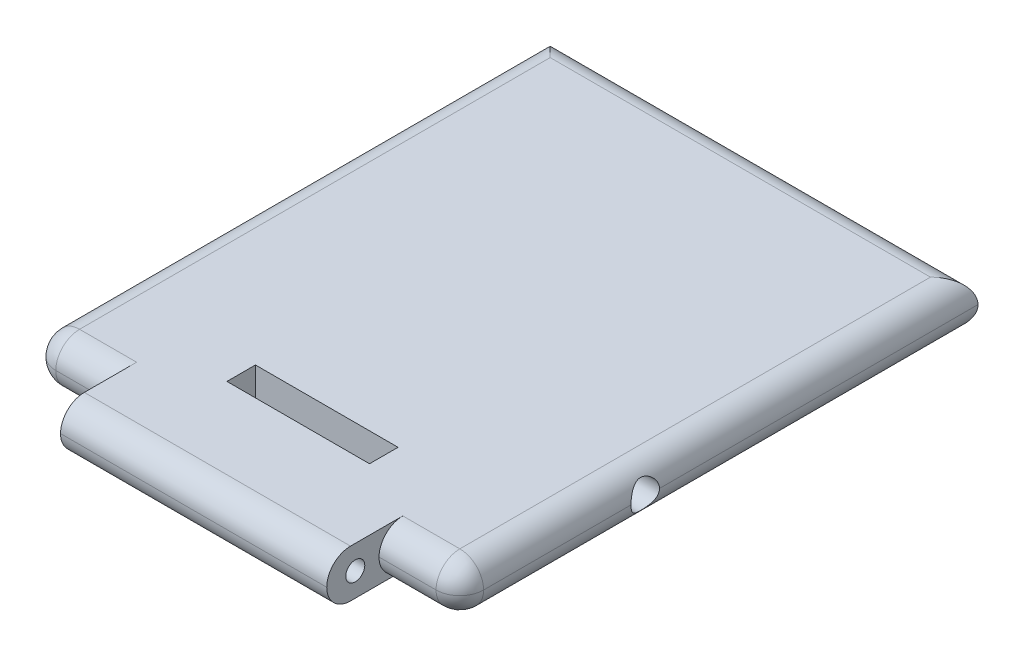
SolidWorks part; units mm, degrees
ref_plane "Front Plane" through (0, 0, 0) normal (0, 0, 1) x (1, 0, 0)
ref_plane "Top Plane" through (0, 0, 0) normal (0, 1, 0) x (1, 0, 0)
ref_plane "Right Plane" through (0, 0, 0) normal (1, 0, 0) x (0, 0, -1)
sketch "Sketch1" plane through (0, 0, 0) normal (0, 1, 0) x (1, 0, 0)
  line L1 (-22.5, 30) -> (22.5, 30)
  line L2 (-22.5, 30) -> (-22.5, -30)
  line L3 (-22.5, -30) -> (22.5, -30)
  line L4 (22.5, 30) -> (22.5, -30)
  line L5 (-22.5, 30) -> (22.5, -30) construction
  line L6 (-22.5, -30) -> (22.5, 30) construction
  point P0 (0, 0)
  dimension "D1" = 60
  dimension "D2" = 45
extrude "Boss-Extrude1" add sketch "Sketch1" along normal mid plane 5
sketch "Sketch2" plane through (0, 2.5, 0) normal (0, 1, 0) x (1, 0, 0)
  line L0 (-22.5, -30) -> (22.5, -30) construction
  line L2 (-14, -30) -> (-14, -24.5)
  line L4 (14, -30) -> (14, -24.5)
  line L9 (-22.5, 30) -> (-22.5, -30) construction
  line L10 (22.5, -30) -> (22.5, 30) construction
  line L11 (-14, -24.5) -> (-22.5, -24.5)
  line L12 (14, -24.5) -> (22.5, -24.5)
  line M5 (22.5, -30) -> (22.5, 30)
  line M7 (-22.5, 30) -> (-22.5, -30)
  line M8 (-22.5, -30) -> (22.5, -30)
  dimension "D1" = 5.5
  dimension "D2" = 8.5
  dimension "D3" = 8.5
  dimension "D4" = 5.5
extrude "Cut-Extrude1" cut sketch "Sketch2" against normal through all both and the other way through all contours L2 L11 M7 M8 | L12 L4 M8 M5
sketch "Sketch9" plane through (-14, 0, 0) normal (-1, 0, 0) x (0, 0, 1)
  line L0 (30, -2.5) -> (30, 2.5) construction
  line L1 (24.5, -2.5) -> (24.5, 2.5) construction
  circle A0 centre (27, 0) radius 1
  point P7 (24.5, 0)
  dimension "D1" = 2
  dimension "D2" = 3
extrude "Cut-Extrude2" cut sketch "Sketch9" against normal through all both and the other way through all
fillet "Fillet1" radius 2.5 12 edges at (0, -2.5, 30) (0, 2.5, 30) (18.25, -2.5, 24.5) (18.25, 2.5, 24.5) (-18.25, -2.5, 24.5) (-22.5, 2.5, -2.75) (-18.25, 2.5, 24.5) (22.5, -2.5, -2.75) (22.5, 2.5, -2.75) (0, -2.5, -30) (0, 2.5, -30) (-22.5, -2.5, -2.75)
ref_plane "Plane2" through (20, 0, 0) normal (1, 0, 0) x (0, 0, -1)
sketch "Sketch11" plane through (20, 0, 0) normal (1, 0, 0) x (0, 0, -1)
  line L0 (30, 0) -> (-22, 0) construction
  circle A0 centre (-5, 0) radius 1.5
  dimension "D1" = 3
  dimension "D2" = 25
sketch "Sketch13" plane through (0, -2.5, 0) normal (0, -1, 0) x (1, 0, 0)
  line L0 (14, 27.5) -> (-14, 27.5) construction
  line L1 (-7.5, 19) -> (7.5, 19)
  line L2 (-7.5, 19) -> (-7.5, 16)
  line L3 (-7.5, 16) -> (7.5, 16)
  line L4 (7.5, 19) -> (7.5, 16)
  line L5 (-7.5, 19) -> (7.5, 16) construction
  line L6 (-7.5, 16) -> (7.5, 19) construction
  line L7 (20, 22) -> (14, 22) construction
  point P0 (0, 17.5)
  point P7 (0, 27.5)
  point P8 (0, 16)
  dimension "D1" = 3
  dimension "D2" = 15
  dimension "D3" = 3
extrude "Cut-Extrude3" cut sketch "Sketch13" against normal through all both and the other way through all
extrude "Cut-Extrude4" cut sketch "Sketch11" along normal through all and the other way blind 6
mirror "Mirror1" about plane through (0, 0, 0) normal (1, 0, 0) of "Cut-Extrude4"
